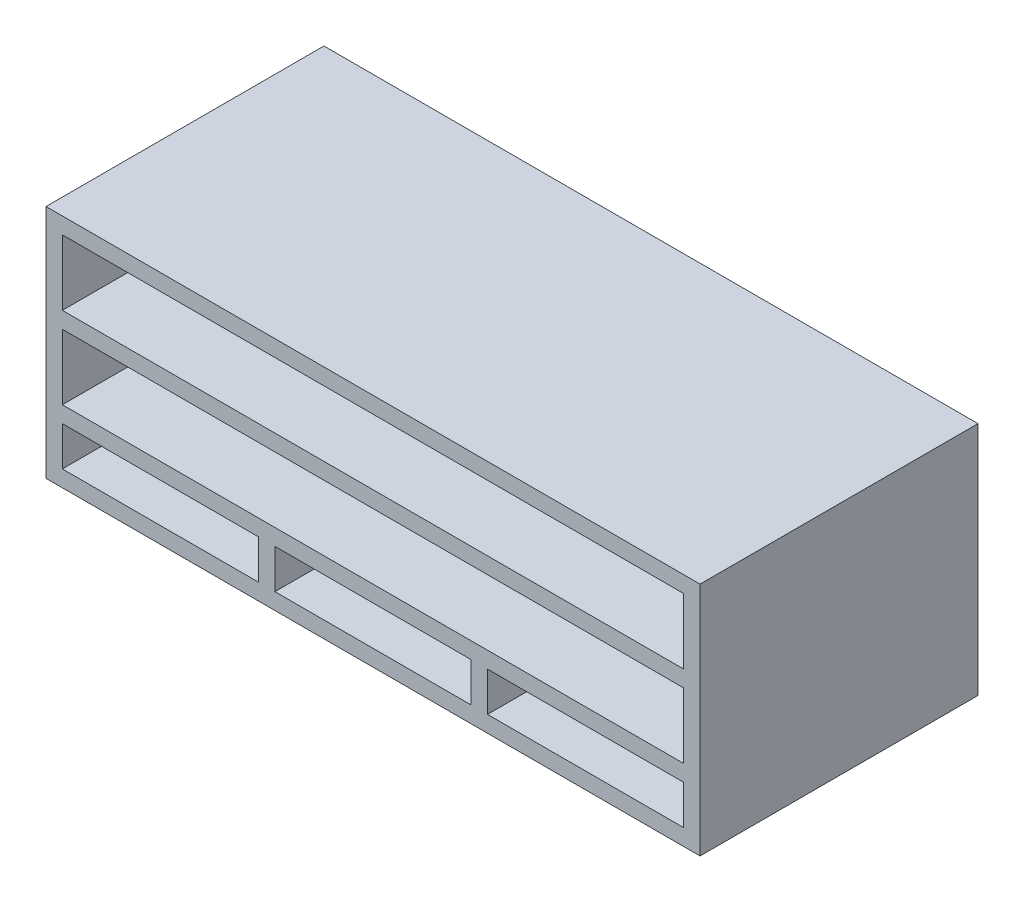
SolidWorks part; units mm, degrees
ref_plane "Front Plane" through (0, 0, 0) normal (0, 0, 1) x (1, 0, 0)
ref_plane "Top Plane" through (0, 0, 0) normal (0, 1, 0) x (1, 0, 0)
ref_plane "Right Plane" through (0, 0, 0) normal (1, 0, 0) x (0, 0, -1)
sketch "Sketch1" plane through (0, 0, 0) normal (0, 0, 1) x (1, 0, 0)
  line L1 (0, 0) -> (-127, 0)
  line L2 (0, 0) -> (0, 45.72)
  line L3 (0, 45.72) -> (-127, 45.72)
  line L4 (-127, 0) -> (-127, 45.72)
  line L5 (-123.825, 42.545) -> (-3.175, 42.545)
  line L6 (-123.825, 42.545) -> (-123.825, 29.845)
  line L7 (-123.825, 29.845) -> (-3.175, 29.845)
  line L8 (-3.175, 42.545) -> (-3.175, 29.845)
  line L9 (-123.825, 26.67) -> (-3.175, 26.67)
  line L10 (-123.825, 26.67) -> (-123.825, 13.97)
  line L11 (-123.825, 13.97) -> (-3.175, 13.97)
  line L12 (-3.175, 26.67) -> (-3.175, 13.97)
  line L13 (-123.825, 10.795) -> (-85.725, 10.795)
  line L14 (-123.825, 10.795) -> (-123.825, 3.175)
  line L15 (-123.825, 3.175) -> (-85.725, 3.175)
  line L16 (-85.725, 10.795) -> (-85.725, 3.175)
  line L17 (-82.55, 10.795) -> (-44.45, 10.795)
  line L18 (-82.55, 10.795) -> (-82.55, 3.175)
  line L19 (-82.55, 3.175) -> (-44.45, 3.175)
  line L20 (-44.45, 10.795) -> (-44.45, 3.175)
  line L21 (-41.275, 10.795) -> (-3.175, 10.795)
  line L22 (-41.275, 10.795) -> (-41.275, 3.175)
  line L23 (-41.275, 3.175) -> (-3.175, 3.175)
  line L24 (-3.175, 10.795) -> (-3.175, 3.175)
  point P25 (-123.825, 6.985)
  point P26 (-82.55, 6.985)
  dimension "D1" = 120.65
  dimension "D2" = 3.175
  dimension "D3" = 3.175
  dimension "D4" = 12.7
  dimension "D5" = 12.7
  dimension "D6" = 3.175
  dimension "D7" = 3.175
  dimension "D8" = 3.175
  dimension "D9" = 7.62
  dimension "D10" = 38.1
  dimension "D11" = 38.1
  dimension "D12" = 38.1
  dimension "D13" = 3.175
  dimension "D14" = 3.175
  dimension "D15" = 3.175
  dimension "D16" = 3.175
extrude "Boss-Extrude1" add sketch "Sketch1" along normal blind 50.8
sketch "Sketch2" plane through (0, 0, 0) normal (0, 0, -1) x (-1, 0, 0)
  line L1 (0, 0) -> (127, 0)
  line L2 (0, 0) -> (0, 45.72)
  line L3 (0, 45.72) -> (127, 45.72)
  line L4 (127, 0) -> (127, 45.72)
extrude "Boss-Extrude2" add sketch "Sketch2" along normal blind 3.175
